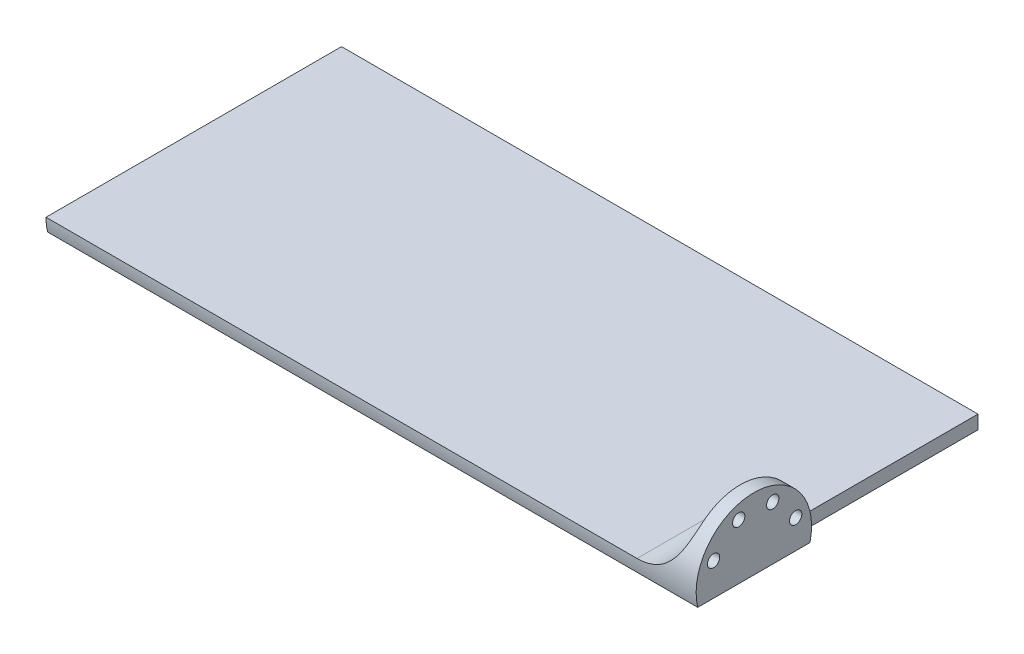
SolidWorks part; units mm, degrees
ref_plane "Front" through (0, 0, 0) normal (0, 0, 1) x (1, 0, 0)
ref_plane "Top" through (0, 0, 0) normal (0, 1, 0) x (1, 0, 0)
ref_plane "Right" through (0, 0, 0) normal (1, 0, 0) x (0, 0, -1)
sketch "Sketch1" plane through (-8.8838, 0, 0) normal (-1, 0, 0) x (0, 0, 1)
  line L0 (88.6962, 49.3856) -> (63.3038, 49.3856) construction
  line L1 (88.3367, 46.3856) -> (63.6633, 46.3856)
  arc A1 (88.3367, 46.3856) -> (63.6633, 46.3856) centre (76, 49.3856) ccw
  circle A3 centre (79.3295, 58.5803) radius 1.3525
  circle A7 centre (66.8053, 52.7151) radius 1.3525
  circle A8 centre (71.8527, 58.2415) radius 1.3525
  circle A9 centre (84.856, 53.5329) radius 1.3525
  dimension "D2" = 3
  dimension "D1" = 25.3924
extrude "Boss-Extrude1" add sketch "Sketch1" along normal blind 3
sketch "Sketch2" plane through (-11.8838, 0, 0) normal (-1, 0, 0) x (0, 0, 1)
  line L2 (88.3367, 46.3856) -> (23.6962, 46.3856)
  line L3 (88.6962, 49.3856) -> (23.6962, 49.3856)
  line L4 (23.6962, 49.3856) -> (23.6962, 46.3856)
  arc A0 (88.3367, 46.3856) -> (63.6633, 46.3856) centre (76, 49.3856) ccw construction
  arc A1 (88.3367, 46.3856) -> (88.6962, 49.3856) centre (76, 49.3856) ccw
  dimension "D1" = 65
extrude "Boss-Extrude2" add sketch "Sketch2" along normal blind 140
fillet "Fillet1" radius 10 1 edges at (-11.8838, 49.3856, 76)
